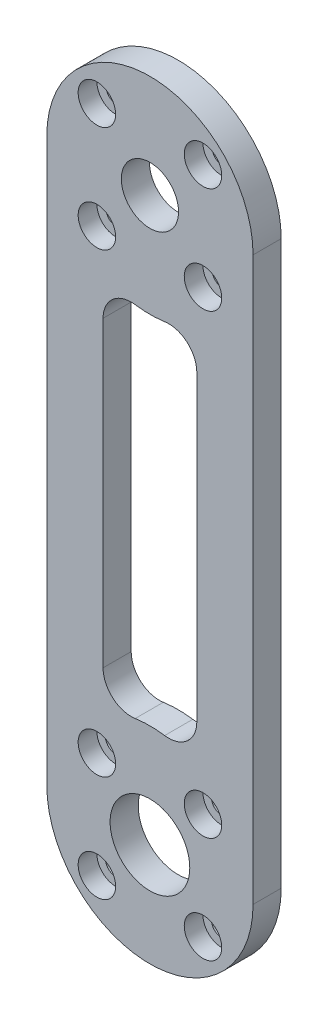
SolidWorks part; units mm, degrees
note: The reader was unsure of these and kept them because the rebuilt part matched: shared geometry of "Sketch3<6>", "Sketch2<5>".
ref_plane "Front Plane" through (0, 0, 0) normal (0, 0, 1) x (1, 0, 0)
ref_plane "Top Plane" through (0, 0, 0) normal (0, 1, 0) x (1, 0, 0)
ref_plane "Right Plane" through (0, 0, 0) normal (1, 0, 0) x (0, 0, -1)
sketch "Sketch1" plane through (0, 0, 0) normal (0, 0, 1) x (1, 0, 0)
  line L0 (0, 30) -> (0, -30) construction
  line L2 (11, 30) -> (11, -30)
  line L4 (-11, 30) -> (-11, -30)
  line L7 (-5, 20.202) -> (-5, -20.202)
  line L9 (5, 20.202) -> (5, -20.202)
  circle A0 centre (0, 30) radius 11
  circle A1 centre (0, -30) radius 11
  point P0 (0, 0)
  point P2 (0, 0)
  dimension "D3" = 22
  dimension "D1" = 60
  dimension "D5" = 6
  dimension "D2" = 22
  dimension "D6" = 6
extrude "Boss-Extrude1" add sketch "Sketch1" along normal blind 3
sketch "Sketch2" plane through (0, 0, 3) normal (0, 0, 1) x (1, 0, 0)
  line L0 (0, 30) -> (5.6569, 35.6569) construction
  line L1 (11, 30) -> (11, -30) construction
  circle A0 centre (0, 30) radius 3.05
  circle A1 centre (5.6569, 35.6569) radius 1
  circle A2 centre (5.6569, 35.6569) radius 2
  dimension "D1" = 6.1
  dimension "D2" = 2
  dimension "D5" = 4
  dimension "D3" = 8
  dimension "D4" = 45
sketch "Sketch3" plane through (0, 0, 3) normal (0, 0, 1) x (1, 0, 0)
  line L0 (5.6569, -24.3431) -> (0, -30) construction
  line L1 (11, 30) -> (11, -30) construction
  circle A0 centre (0, -30) radius 4.25
  circle A1 centre (5.6569, -24.3431) radius 1.1
  circle A2 centre (5.6569, -24.3431) radius 2
  dimension "D2" = 8.5
  dimension "D3" = 2.2
  dimension "D5" = 4
  dimension "D1" = 45
  dimension "D4" = 8
extrude "Cut-Extrude3" cut sketch "Sketch3" against normal up to surface (3 mm away) up to face at (0, 0, 0)
extrude "Cut-Extrude4" cut sketch "Sketch3<6>" against normal offset from surface (2 mm away) 1 up to face at (4.25, -30, 0)
sketch "Sketch3<6>" plane through (0, 0, 3) normal (0, 0, 1) x (1, 0, 0) same geometry as "Sketch3"
pattern_circular "CirPattern3" count 4 over 360 about axis through (0, -30, 0) along (0, 0, 1) of "Cut-Extrude3", "Cut-Extrude4"
extrude "Cut-Extrude5" cut sketch "Sketch2" against normal up to surface (3 mm away) up to face at (-4.5569, -24.3431, 0)
extrude "Cut-Extrude6" cut sketch "Sketch2<5>" against normal offset from surface (2 mm away) 1 up to face at (6.6569, 35.6569, 0)
sketch "Sketch2<5>" plane through (0, 0, 3) normal (0, 0, 1) x (1, 0, 0) same geometry as "Sketch2"
pattern_circular "CirPattern4" count 4 over 360 about axis through (0, 30, 0) along (0, 0, 1) of "Cut-Extrude6", "Cut-Extrude5"
fillet "Fillet1" radius 3 4 edges at (-5, -20.202, 1.5) (5, -20.202, 1.5) (-5, 20.202, 1.5) (5, 20.202, 1.5)
